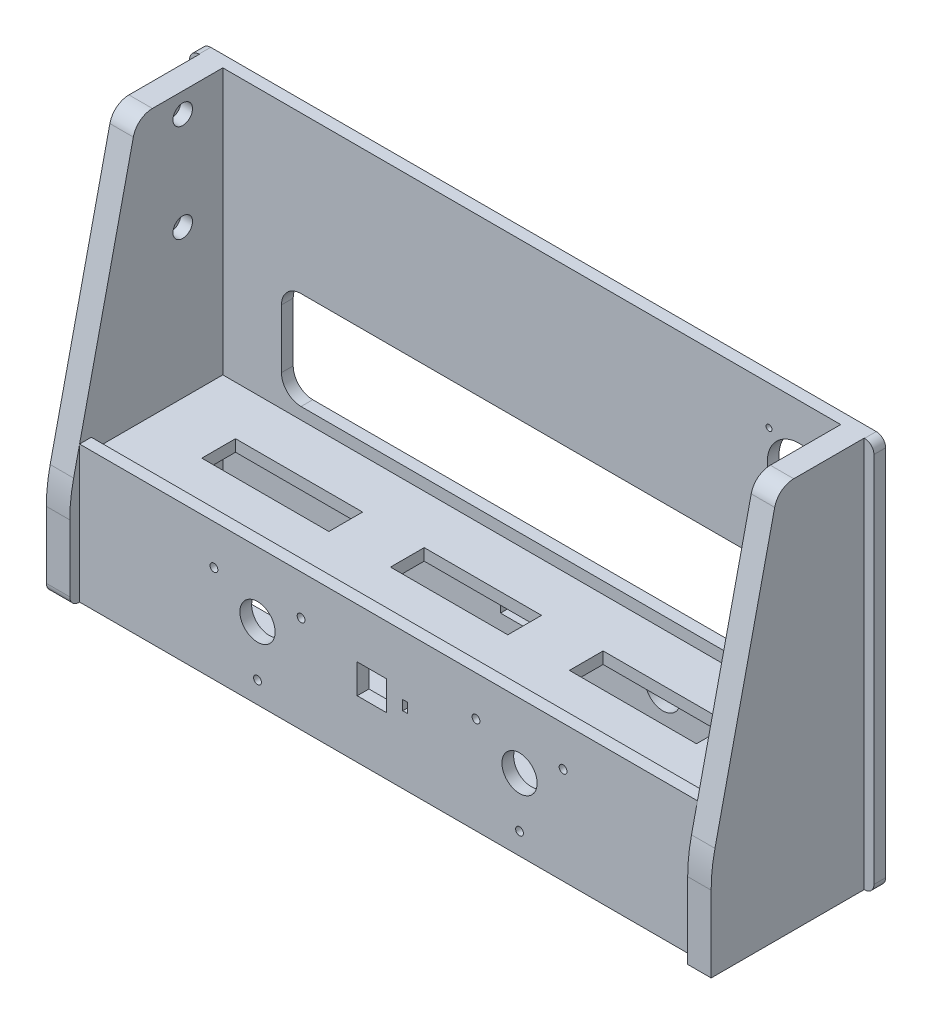
SolidWorks part; units mm, degrees
material "Birch plywood FK"
ref_plane "Спереди" through (0, 0, 0) normal (0, 0, 1) x (1, 0, 0)
ref_plane "Сверху" through (0, 0, 0) normal (0, 1, 0) x (1, 0, 0)
ref_plane "Справа" through (0, 0, 0) normal (1, 0, 0) x (0, 0, -1)
sketch "Эскиз1" plane through (0, 0, 0) normal (1, 0, 0) x (0, 0, -1)
  line L0 (0, 200) -> (0, 0)
  line L1 (0, 0) -> (-95, 0)
  line L2 (-95, 0) -> (-50, 200)
  line L3 (-50, 200) -> (0, 200)
  dimension "D1" = 200
  dimension "D2" = 95
  dimension "D3" = 50
extrude "Бобышка-Вытянуть1" add sketch "Эскиз1" along normal blind 340
sketch "Эскиз2" plane through (0, 200, 0) normal (0, 1, 0) x (1, 0, 0)
  line L0 (170, -95) -> (170, 0) construction
  line L1 (340, -95) -> (0, -95) construction
  line L2 (340, 0) -> (0, 0) construction
  line L3 (340, -50) -> (340, -95) construction
  line L4 (12, -95) -> (328, -95)
  line L5 (12, -95) -> (12, -6)
  line L6 (12, -6) -> (328, -6)
  line L7 (328, -95) -> (328, -6)
  line L8 (12, -95) -> (328, -6) construction
  line L9 (12, -6) -> (328, -95) construction
  point P6 (170, -50.5)
  dimension "D1" = 12
  dimension "D2" = 6
extrude "Вырез-Вытянуть1" cut sketch "Эскиз2" against normal offset from surface (130 mm away) 70 up to face at (170, 0, 47.5)
sketch "Эскиз3" plane through (0, 70, 0) normal (0, 1, 0) x (1, 0, 0)
  line L0 (340, -95) -> (0, -95) construction
  line L1 (12, -79.25) -> (328, -79.25)
  line L2 (12, -79.25) -> (12, -95)
  line L3 (12, -95) -> (328, -95)
  line L4 (328, -79.25) -> (328, -95)
extrude "Вырез-Вытянуть2" cut sketch "Эскиз3" against normal through all
sketch "Эскиз4" plane through (0, 0, 79.25) normal (0, 0, 1) x (1, 0, 0)
  line L0 (170, 70) -> (170, 0) construction
  line L1 (12, 70) -> (328, 70) construction
  line L2 (328, 0) -> (12, 0) construction
  line L3 (12, 0) -> (12, 70) construction
  line L4 (328, 12) -> (12, 12)
  line L5 (328, 12) -> (328, 58)
  line L6 (328, 58) -> (12, 58)
  line L7 (12, 12) -> (12, 58)
  line L8 (328, 12) -> (12, 58) construction
  line L9 (328, 58) -> (12, 12) construction
  line L10 (12, 70) -> (328, 70) construction
  line L12 (328, 64) -> (12, 64)
  line L13 (328, 64) -> (328, 70)
  line L14 (328, 70) -> (12, 70)
  line L15 (12, 64) -> (12, 70)
  line L16 (328, 64) -> (12, 70) construction
  line L17 (328, 70) -> (12, 64) construction
  line L18 (328, 6) -> (12, 6)
  line L19 (328, 6) -> (328, 0)
  line L20 (328, 0) -> (12, 0)
  line L21 (12, 6) -> (12, 0)
  line L22 (328, 6) -> (12, 0) construction
  line L23 (328, 0) -> (12, 6) construction
  point P6 (170, 35)
  point P15 (170, 67)
  point P21 (170, 3)
  dimension "D1" = 12
  dimension "D2" = 6
extrude "Вырез-Вытянуть3" cut sketch "Эскиз4" against normal offset from surface (67.25 mm away) 6 from offset 6 up to face at (170, 100, 0) offset against normal yes
sketch "Эскиз5" plane through (0, 0, 6) normal (0, 0, 1) x (1, 0, 0)
  line L0 (170, 200) -> (170, 70) construction
  line L1 (328, 200) -> (12, 200) construction
  line L2 (12, 70) -> (328, 70) construction
  line L3 (12, 64) -> (12, 200) construction
  line L4 (298, 70) -> (42, 70)
  line L5 (298, 70) -> (298, 120)
  line L6 (298, 120) -> (42, 120)
  line L7 (42, 70) -> (42, 120)
  line L8 (298, 70) -> (42, 120) construction
  line L9 (298, 120) -> (42, 70) construction
  point P6 (170, 95)
  dimension "D1" = 30
  dimension "D2" = 50
extrude "Вырез-Вытянуть4" cut sketch "Эскиз5" against normal through all
sketch "Эскиз6" plane through (0, 70, 0) normal (0, 1, 0) x (1, 0, 0)
  line L0 (170, 0) -> (170, -79.25) construction
  line L1 (42, 0) -> (298, 0) construction
  line L2 (12, -79.25) -> (328, -79.25) construction
  line L3 (12, -6) -> (42, -6) construction
  line L4 (140, -39.625) -> (12, -39.625) construction
  line L5 (12, -6) -> (12, -73.25) construction
  line L6 (200, -48.25) -> (140, -48.25)
  line L7 (200, -48.25) -> (200, -31)
  line L8 (200, -31) -> (140, -31)
  line L9 (140, -48.25) -> (140, -31)
  line L10 (200, -48.25) -> (140, -31) construction
  line L11 (200, -31) -> (140, -48.25) construction
  line L13 (108.5, -31) -> (43.5, -31)
  line L14 (328, -6) -> (328, -73.25) construction
  line L15 (328, -39.625) -> (200, -39.625) construction
  line L16 (108.5, -31) -> (108.5, -48.25)
  line L17 (108.5, -48.25) -> (43.5, -48.25)
  line L19 (43.5, -31) -> (43.5, -48.25)
  line L20 (108.5, -31) -> (43.5, -48.25) construction
  line L21 (108.5, -48.25) -> (43.5, -31) construction
  line L22 (296.5, -31) -> (231.5, -31)
  line L23 (296.5, -31) -> (296.5, -48.25)
  line L24 (296.5, -48.25) -> (231.5, -48.25)
  line L25 (231.5, -31) -> (231.5, -48.25)
  line L26 (296.5, -31) -> (231.5, -48.25) construction
  line L27 (296.5, -48.25) -> (231.5, -31) construction
  point P6 (170, -39.625)
  point P18 (76, -39.625)
  point P28 (264, -39.625)
  dimension "D1" = 25
  dimension "D2" = 60
  dimension "D3" = 65
extrude "Вырез-Вытянуть5" cut sketch "Эскиз6" against normal through all
sketch "Эскиз8" plane through (0, 0, 0) normal (-1, 0, 0) x (0, 0, 1)
  line L0 (95, 0) -> (0, 0) construction
  line L1 (84.25, 70) -> (95, 70)
  line L2 (84.25, 70) -> (84.25, 0)
  line L3 (84.25, 0) -> (95, 0)
  line L4 (95, 70) -> (95, 0)
  line L5 (79.25, 0) -> (79.25, 70) construction
  line L6 (79.25, 70) -> (73.25, 70) construction
  dimension "D1" = 5
extrude "Вырез-Вытянуть7" cut sketch "Эскиз8" against normal through all
sketch "Эскиз10" plane through (0, 200, 0) normal (0, 1, 0) x (1, 0, 0)
  line L0 (328, -6) -> (12, -6) construction
  line L1 (0, 0) -> (-5, 0)
  line L2 (0, 0) -> (0, -6)
  line L3 (0, -6) -> (-5, -6)
  line L4 (-5, 0) -> (-5, -6)
  line L5 (340, 0) -> (345, 0)
  line L6 (340, 0) -> (340, -6)
  line L7 (340, -6) -> (345, -6)
  line L8 (345, 0) -> (345, -6)
  dimension "D1" = 5
  dimension "D2" = 5
extrude "Бобышка-Вытянуть3" add sketch "Эскиз10" against normal up to surface (200 mm away) up to face at (170, 0, 61.9375)
sketch "Эскиз12" plane through (0, 0, 0) normal (-1, 0, 0) x (0, 0, 1)
  circle A0 centre (26.5, 189.7) radius 5
  circle A1 centre (26.5, 139.7) radius 5
  dimension "D1" = 10
extrude "Вырез-Вытянуть9" cut sketch "Эскиз12" against normal offset from surface (328 mm away) 6 from offset 6 up to face at (340, 69.5556, 49.525) offset against normal yes
sketch "Эскиз13" plane through (0, 0, 6) normal (0, 0, 1) x (1, 0, 0)
  line L0 (334, 184.7) -> (345, 184.7) construction
  line L1 (345, 0) -> (345, 200) construction
  line L2 (306.85, 184.7) -> (306.85, 144.7) construction
  line L3 (334, 144.7) -> (345, 144.7) construction
  line L4 (306.85, 164.7) -> (345, 164.7) construction
  circle A0 centre (306.85, 164.7) radius 16.4
  circle A2 centre (291.35, 180.2) radius 1.5
  circle A3 centre (322.35, 180.2) radius 1.5
  circle A4 centre (322.35, 149.2) radius 1.5
  circle A5 centre (291.35, 149.2) radius 1.5
  circle A6 centre (306.85, 164.7) radius 16.4 construction
  point P0 (306.85, 164.7)
  dimension "D1" = 3
extrude "Вырез-Вытянуть10" cut sketch "Эскиз13" against normal through all
fillet "Скругление2" radius 10 2 edges at (6, 200, 50) (334, 200, 50)
fillet "Скругление4" radius 80 2 edges at (334, 47.7778, 84.25) (6, 47.7778, 84.25)
sketch "Эскиз16" plane through (0, 0, 79.25) normal (0, 0, 1) x (1, 0, 0)
  circle A0 centre (103, 36.7238) radius 9
  circle A1 centre (237, 36.7238) radius 9
  dimension "D1" = 18
extrude "Вырез-Вытянуть12" cut sketch "Эскиз16" against normal through all
sketch "Эскиз19" plane through (0, 0, 79.25) normal (0, 0, 1) x (1, 0, 0)
  line L0 (161.5, 37) -> (178.5, 37) construction
  line L1 (169, 29.5) -> (154, 29.5)
  line L2 (169, 29.5) -> (169, 44.5)
  line L3 (169, 44.5) -> (154, 44.5)
  line L4 (154, 29.5) -> (154, 44.5)
  line L5 (169, 29.5) -> (154, 44.5) construction
  line L6 (169, 44.5) -> (154, 29.5) construction
  line L7 (179.75, 34.5) -> (177.25, 34.5)
  line L8 (179.75, 34.5) -> (179.75, 39.5)
  line L9 (179.75, 39.5) -> (177.25, 39.5)
  line L10 (177.25, 34.5) -> (177.25, 39.5)
  line L11 (179.75, 34.5) -> (177.25, 39.5) construction
  line L12 (179.75, 39.5) -> (177.25, 34.5) construction
  line L13 (170, 37) -> (170, -29) construction
  line L14 (153.0926, -29) -> (186.9074, -29) construction
  line L15 (60, 24.5) -> (280, 24.5) construction
  circle A0 centre (125.2775, 49.5857) radius 2
  circle A1 centre (80.7225, 49.5857) radius 2
  circle A2 centre (103, 11) radius 2
  circle A3 centre (214.7225, 49.5857) radius 2
  circle A4 centre (259.2775, 49.5857) radius 2
  circle A5 centre (237, 11) radius 2
  point P0 (161.5, 37)
  point P5 (178.5, 37)
  dimension "D7" = 4
  dimension "D1" = 5
  dimension "D2" = 2.5
  dimension "D3" = 12.5
  dimension "D4" = 17
  dimension "D5" = 15
  dimension "D6" = 15
extrude "Вырез-Вытянуть15" cut sketch "Эскиз19" against normal through all
fillet "Скругление5" radius 4.8 5 edges at (-5, 200, 3) (6, 0, 84.25) (-5, 0, 3) (345, 0, 3) (345, 200, 3)
fillet "Скругление6" radius 10 4 edges at (298, 70, 3) (298, 120, 3) (42, 70, 3) (42, 120, 3)
sketch "Эскиз20" plane through (0, 0, 6) normal (0, 0, 1) x (1, 0, 0)
  line L0 (319.5142, 124.6) -> (309.5142, 124.6) construction
  line L1 (319.5142, 124.1) -> (309.5142, 124.1)
  line L2 (319.5142, 125.1) -> (309.5142, 125.1)
  line L3 (319.5142, 115.1) -> (309.5142, 115.1) construction
  line L4 (319.5142, 114.6) -> (309.5142, 114.6)
  line L5 (319.5142, 115.6) -> (309.5142, 115.6)
  arc A0 (319.5142, 124.1) -> (319.5142, 125.1) centre (319.5142, 124.6) ccw
  arc A1 (309.5142, 125.1) -> (309.5142, 124.1) centre (309.5142, 124.6) ccw
  arc A2 (319.5142, 114.6) -> (319.5142, 115.6) centre (319.5142, 115.1) ccw
  arc A3 (309.5142, 115.6) -> (309.5142, 114.6) centre (309.5142, 115.1) ccw
  point P2 (314.5142, 124.6)
  point P7 (314.5142, 115.1)
  dimension "D1" = 1
  dimension "D2" = 10
extrude "Вырез-Вытянуть16" cut sketch "Эскиз20" against normal through all
